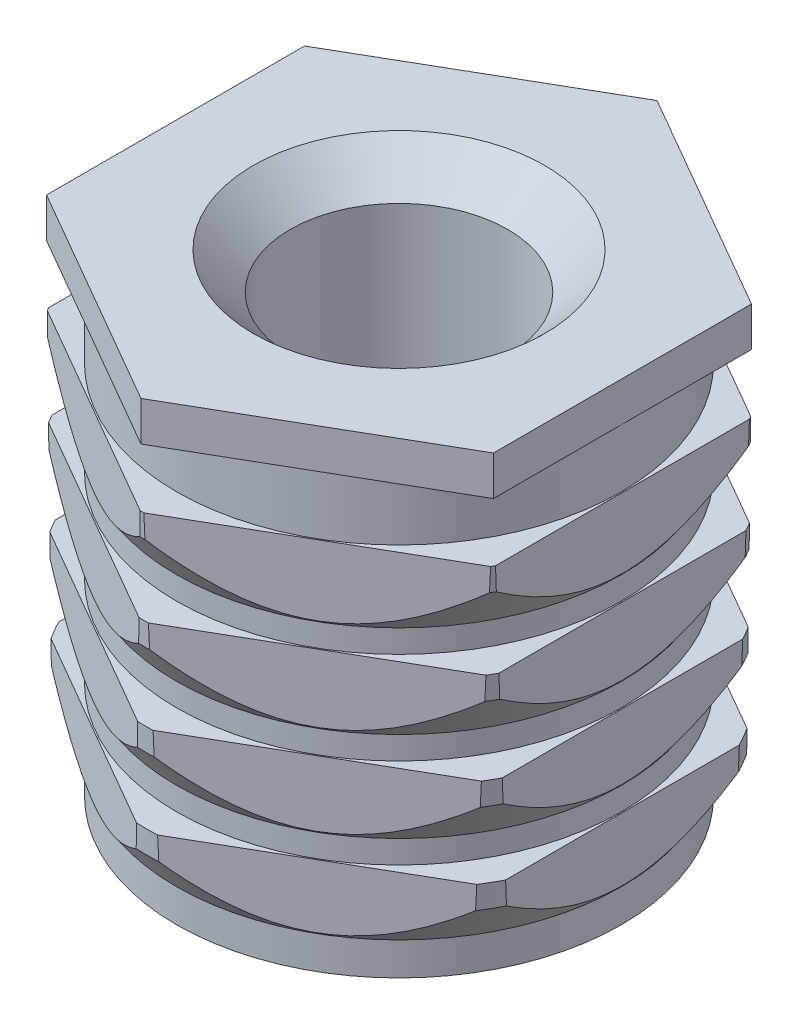
SolidWorks part; units mm, degrees
ref_plane "Front Plane" through (0, 0, 0) normal (0, 0, 1) x (1, 0, 0)
ref_plane "Top Plane" through (0, 0, 0) normal (0, 1, 0) x (1, 0, 0)
ref_plane "Right Plane" through (0, 0, 0) normal (1, 0, 0) x (0, 0, -1)
sketch "Sketch1" plane through (0, 0, 0) normal (0, 1, 0) x (1, 0, 0)
  line L0 (-3.16, 0) -> (3.16, 0) construction
  line L1 (-3.16, 0) -> (-3.175, 0) construction
  line L2 (0, 3.6662) -> (-3.175, 1.8331)
  line L3 (-3.175, 1.8331) -> (-3.175, -1.8331)
  line L4 (-3.175, -1.8331) -> (0, -3.6662)
  line L5 (0, -3.6662) -> (3.175, -1.8331)
  line L6 (3.175, -1.8331) -> (3.175, 1.8331)
  line L7 (3.175, 1.8331) -> (0, 3.6662)
  line L8 (3.16, 0) -> (3.175, 0) construction
  line L9 (-3.6662, 0) -> (-3.175, 0) construction
  circle A0 centre (0, 0) radius 3.16 construction
  circle A1 centre (0, 0) radius 3.175 construction
  circle A2 centre (0, 0) radius 3.6662 construction
  dimension "OD" = 6.32
  dimension "Hex" = 6.35
extrude "Extrude1" add sketch "Sketch1" against normal blind 6.73
sketch "Sketch2" plane through (0, 0, 0) normal (0, 1, 0) x (1, 0, 0)
  circle A2 centre (0, 0) radius 2
  point P0 (-2, 0)
  dimension "Internal Thread OD" = 4
curve "Helix/Spiral1" pitch 0.7 height 7.9681 turns 11.383 parameters "Internal Thread Height"=7.9681, "Internal Thread Pitch"=0.7
sketch "Sketch3" plane through (0, 0, 0) normal (0, 0, 1) x (1, 0, 0)
  line L0 (-1.4696, 0.3937) -> (-1.4696, -0.3063) construction
  line L1 (-1.4696, -0.3063) -> (-2.0758, 0.0438) construction
  line L2 (-2.0758, 0.0438) -> (-1.4696, 0.3937) construction
  line L3 (-1.4696, 0.0438) -> (-1.5453, 0.0437) construction
  line L4 (-1.5453, 0.0437) -> (-2, 0.0438) construction
  line L5 (-2, 0.0438) -> (-2.0758, 0.0438) construction
  line L6 (-2, 0.0875) -> (-2, 0)
  line L7 (-1.5453, -0.2625) -> (-1.5453, 0.35) construction
  line L11 (-2, 0) -> (-1.5074, -0.2844)
  line L12 (-1.5074, -0.2844) -> (-1.5074, 0.3719)
  line L13 (-1.5074, 0.3719) -> (-2, 0.0875)
  point P18 (-1.5074, 0.0437)
  dimension "D1" = 0.7
  dimension "D2" = 0.0875
sketch "Sketch4" plane through (0, 0, 0) normal (0, 1, 0) x (-1, 0, 0)
  circle A0 centre (0, 0) radius 1.5453
extrude "Extrude2" cut sketch "Sketch4" against normal through all
chamfer "Chamfer1" distance 0.525 angle 45 2 edges at (0, 0, 1.5453) (0, -6.73, 1.5453)
sketch "Sketch5" plane through (0, 0, 0) normal (0, 0, 1) x (1, 0, 0)
  line L0 (3.6662, 0) -> (-3.6662, 0) construction
  line L1 (-3.16, 0) -> (-3.16, -6.73) construction
  line L2 (-3.16, 0) -> (-3.6662, 0) construction
  line L3 (0, 0) -> (0, -6.73) construction
  line L4 (-3.175, -6.73) -> (0, -6.73) construction
  line L5 (-3.16, -6.73) -> (-3.6662, -6.73)
  line L6 (-3.6662, 0) -> (-3.175, 0) construction
  line L7 (-3.6662, 0) -> (-3.6662, -6.73) construction
  line L8 (-3.6662, -0.5608) -> (-3.5585, -6.73) construction
  line L9 (-3.6662, -0.5608) -> (-3.16, -0.5608)
  line L10 (-3.6662, 0) -> (-3.6662, -0.5608)
  line L11 (-3.16, -0.5608) -> (-3.16, -1.4021)
  line L12 (-3.5994, -4.3866) -> (-3.16, -5.0141)
  line L13 (-3.16, -6.73) -> (-3.16, -6.262)
  line L14 (-3.16, -5.0141) -> (-3.16, -5.3403)
  line L15 (-3.16, -1.4021) -> (-3.6515, -1.4021)
  line L16 (-3.6515, -1.4021) -> (-3.6458, -1.7282)
  line L17 (-3.6458, -1.7282) -> (-3.16, -2.422)
  line L18 (-3.16, -5.3403) -> (-3.5827, -5.3403)
  line L19 (-3.6662, 0) -> (-4.1723, 0)
  line L20 (-4.1723, 0) -> (-4.1723, -6.73)
  line L21 (-4.1723, -6.73) -> (-3.6662, -6.73)
  line L22 (-3.16, -2.7481) -> (-3.628, -2.7481)
  line L23 (-3.16, -2.422) -> (-3.16, -2.7481)
  line L24 (-3.628, -2.7481) -> (-3.6223, -3.0742)
  line L25 (-3.6223, -3.0742) -> (-3.16, -3.7344)
  line L26 (-3.16, -4.0605) -> (-3.6051, -4.0605)
  line L27 (-3.6051, -4.0605) -> (-3.5994, -4.3866)
  line L28 (-3.5827, -5.3403) -> (-3.5771, -5.6663)
  line L29 (-3.16, -3.7344) -> (-3.16, -4.0605)
  line L30 (-3.5771, -5.6663) -> (-3.16, -6.262)
  dimension "D1" = 0.5608
  dimension "D2" = 1
  dimension "D5" = 35
  dimension "D6" = 0.8412
  dimension "D3" = 1.346
revolve "Cut-Revolve1" cut sketch "Sketch5" angle 360 about L3
sketch "Sketch6" plane through (0, 0, 0) normal (0, 1, 0) x (1, 0, 0)
  line L0 (0, 0) -> (1.4639, -1.4639) construction
  line L1 (0, 0) -> (0, -3.6662) construction
  circle A0 centre (0, 0) radius 2.0703 construction
  point P8 (1.4639, -1.4639)
  dimension "D1" = 45
ref_plane "Contact Plane 1" through (0, 0, 0) normal (0, 1, 0) x (1, 0, 0)
ref_plane "Contact Plane 2" through (0, -6.73, 0) normal (0, -1, 0) x (-1, 0, 0)
ref_axis "Center Axis 1" through (0, -6.205, 0) along (0, 1, 0)
sweep "Cut-Sweep1" [suppressed] cut profiles "Sketch3" path "Helix/Spiral1"
equation "\"Internal Thread Height@Helix/Spiral1\" = \"Internal Thread Pitch@Helix/Spiral1\" + \"Length@Extrude1\" + 0.5381"
equation "\"D1@Sketch3\" = \"Internal Thread Pitch@Helix/Spiral1\""
equation "\"D2@Sketch3\" = \"D1@Sketch3\" * 1 / 8"
equation "\"D1@Chamfer1\" = \"Internal Thread Pitch@Helix/Spiral1\" * 6 / 8"
equation "\"D1@Sketch5\" = \"Length@Extrude1\"  * 1 / 12"
equation "\"D6@Sketch5\" = \"D1@Sketch5\" * 1.5"
equation "\"D3@Sketch5\" = \"Length@Extrude1\"  * 1 / 5"
